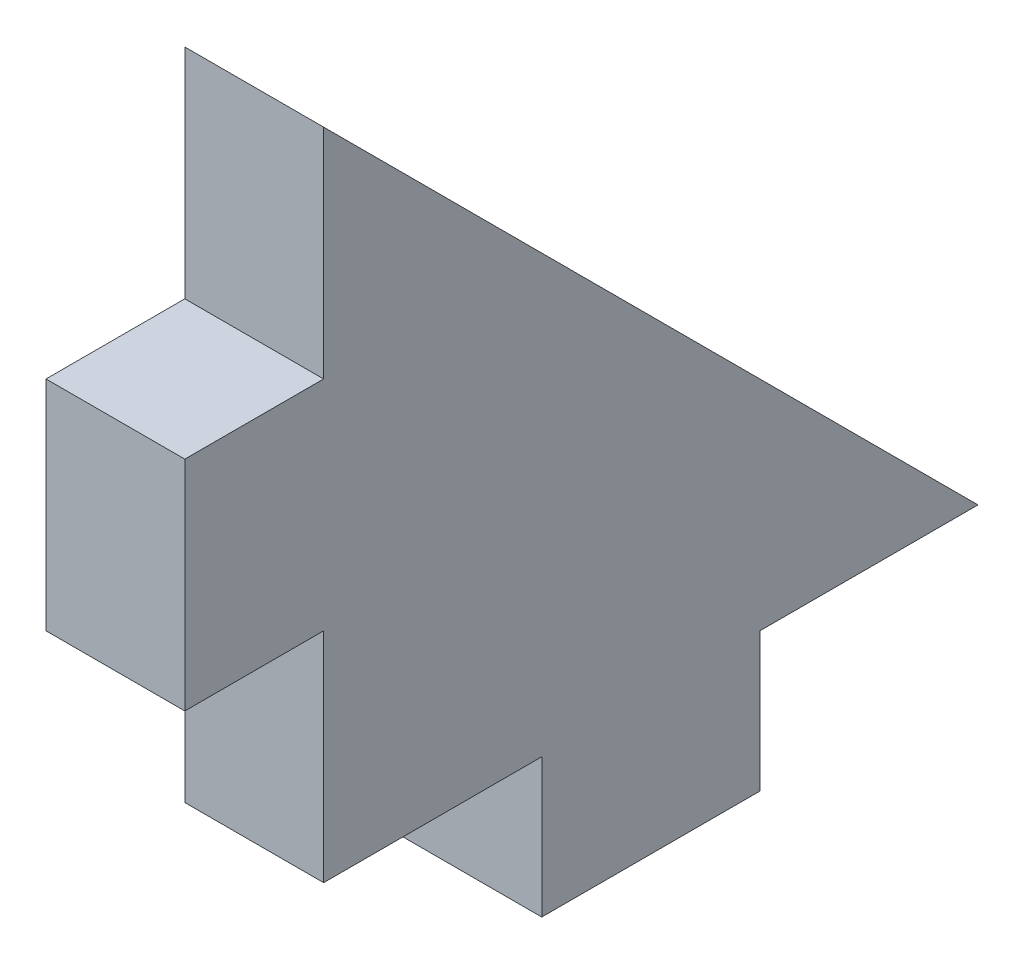
SolidWorks part; units mm, degrees
ref_plane "Front Plane" through (0, 0, 0) normal (0, 0, 1) x (1, 0, 0)
ref_plane "Top Plane" through (0, 0, 0) normal (0, 1, 0) x (1, 0, 0)
ref_plane "Right Plane" through (0, 0, 0) normal (1, 0, 0) x (0, 0, -1)
sketch "Sketch1" plane through (0, 0, 0) normal (1, 0, 0) x (0, 0, -1)
  line L0 (0, 21.2132) -> (21.2132, 0)
  line L1 (0, 0) -> (7.0711, 0)
  line L2 (0, 0) -> (0, 7.0711)
  line L3 (0, 14.1421) -> (0, 21.2132)
  line L4 (0, 14.1421) -> (-4.5, 14.1421)
  line L5 (14.1421, 0) -> (21.2132, 0)
  line L6 (0, 7.0711) -> (-4.5, 7.0711)
  line L7 (-4.5, 14.1421) -> (-4.5, 7.0711)
  line L9 (7.0711, 0) -> (7.0711, -4.5)
  line L10 (7.0711, -4.5) -> (14.1421, -4.5)
  line L11 (14.1421, 0) -> (14.1421, -4.5)
  dimension "D1" = 4.5
  dimension "D2" = 30
extrude "Boss-Extrude1" add sketch "Sketch1" along normal blind 4.5
equation "\"mdf\"=\"mdf@fmv1.assembly\""
equation "\"D1@Sketch1\"=\"mdf\""
equation "\"D1@Boss-Extrude1\"=\"mdf\""
